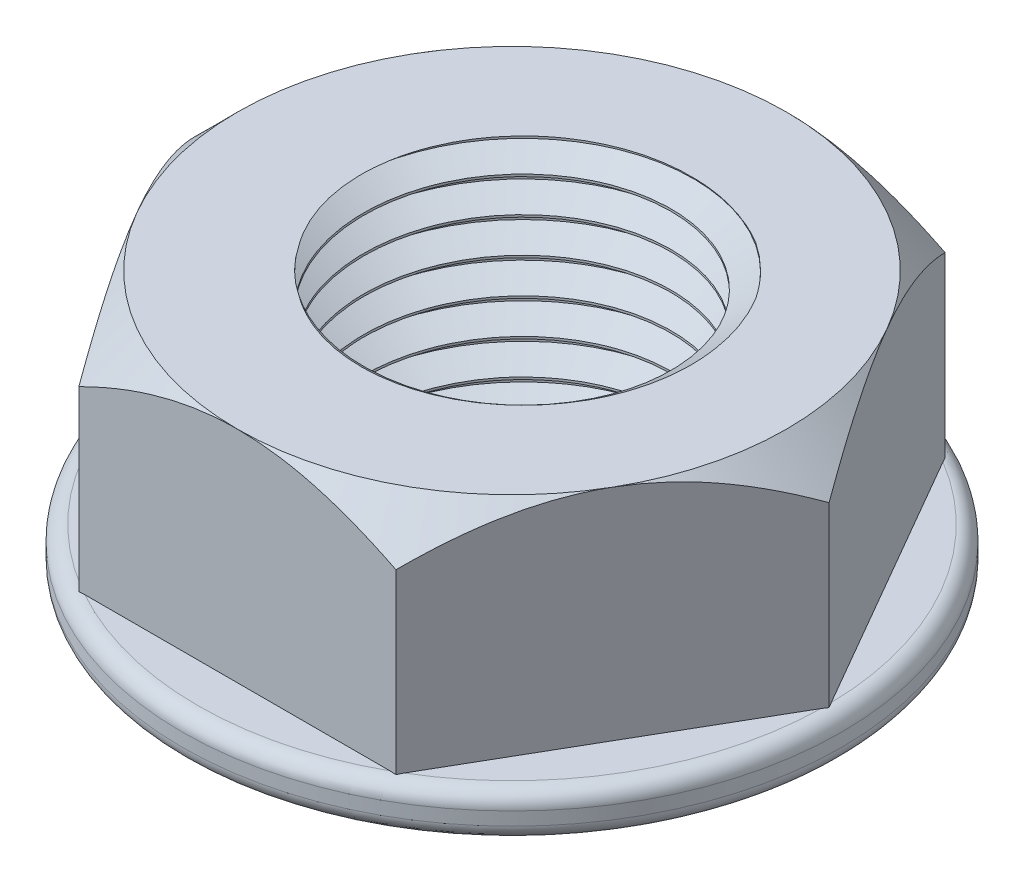
SolidWorks part; units mm, degrees
ref_plane "Front Plane" through (0, 0, 0) normal (0, 0, 1) x (1, 0, 0)
ref_plane "Top Plane" through (0, 0, 0) normal (0, 1, 0) x (1, 0, 0)
ref_plane "Right Plane" through (0, 0, 0) normal (1, 0, 0) x (0, 0, -1)
sketch "Sketch1" plane through (0, 0, 0) normal (0, 1, 0) x (1, 0, 0)
  line L1 (14.4338, 0) -> (7.2169, 12.5)
  line L2 (7.2169, 12.5) -> (-7.2169, 12.5)
  line L3 (-7.2169, 12.5) -> (-14.4338, 0)
  line L4 (-14.4338, 0) -> (-7.2169, -12.5)
  line L5 (-7.2169, -12.5) -> (7.2169, -12.5)
  line L6 (7.2169, -12.5) -> (14.4338, 0)
  circle A0 centre (0, 0) radius 12.5 construction
  dimension "D1" = 25
extrude "Boss-Extrude1" add sketch "Sketch1" along normal blind 10
sketch "Sketch2" plane through (0, 10, 0) normal (0, 1, 0) x (1, 0, 0)
  circle A0 centre (0, 0) radius 12.5
extrude "Cut-Extrude1" cut sketch "Sketch2" against normal blind 10 draft 45 flip side to cut
sketch "Sketch3" plane through (0, 0, 0) normal (0, -1, 0) x (1, 0, 0)
  circle A0 centre (0, 0) radius 15
extrude "Boss-Extrude2" add sketch "Sketch3" along normal blind 2
fillet "Fillet4" radius 0.7 1 edges at (0, -2, -15)
fillet "Fillet5" radius 0.7 1 edges at (0, 0, -15)
sketch "Sketch4" plane through (0, -2, 0) normal (0, -1, 0) x (1, 0, 0)
  circle A0 centre (0, 0) radius 7
  dimension "D1" = 14
extrude "Cut-Extrude2" cut sketch "Sketch4" against normal blind 15
ref_plane "Plane1" through (0, -5, 0) normal (0, 1, 0) x (1, 0, 0)
sketch "Sketch6" plane through (0, -5, 0) normal (0, 1, 0) x (1, 0, 0)
  circle A0 centre (0, 0) radius 7 construction
  circle A1 centre (0, 0) radius 7
curve "Helix/Spiral1" pitch 1.6 height 20 radius 7 left hand yes centre (0, -5, 0) axis (0, 1, 0) start towards (0, 0, 1)
sketch "Sketch7" plane through (0, 0, 0) normal (0, 0, 1) x (1, 0, 0)
  line L0 (-7, 14.95) -> (-7, 13.45)
  line L1 (-7, 13.45) -> (-8, 14.15)
  line L2 (-8, 14.15) -> (-8, 14.25)
  line L3 (-8, 14.25) -> (-7, 14.95)
  point P2 (-8, 14.2)
  point P5 (-7, 14.2)
  dimension "D1" = 1
  dimension "D2" = 0.1
  dimension "D3" = 1.5
sweep "Cut-Sweep1" cut profiles "Sketch7" path "Helix/Spiral1" align with end faces yes
